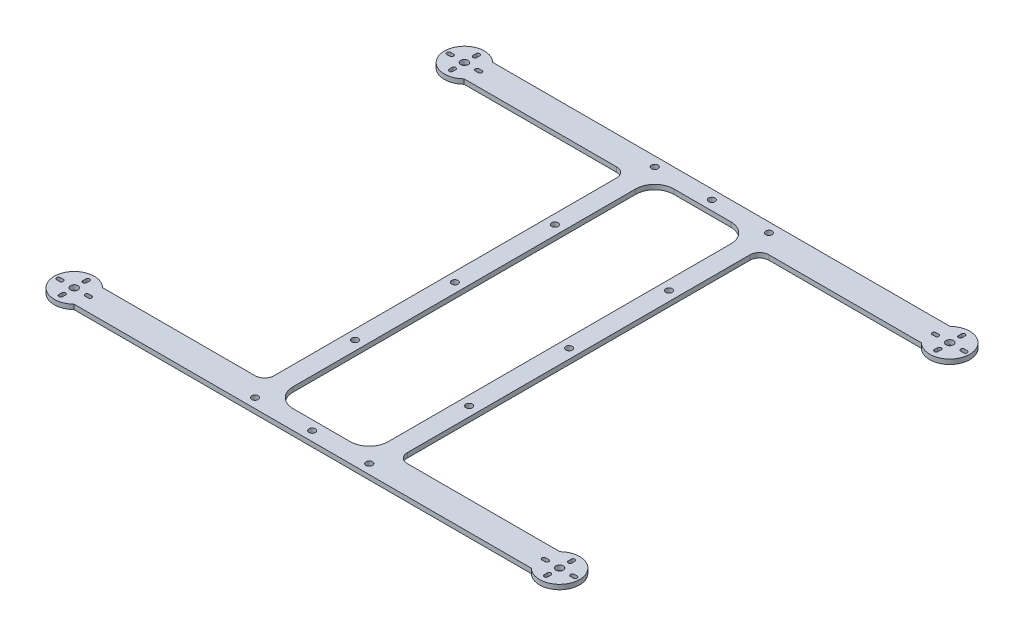
SolidWorks part; units mm, degrees
ref_plane "Front Plane" through (0, 0, 0) normal (0, 0, 1) x (1, 0, 0)
ref_plane "Top Plane" through (0, 0, 0) normal (0, 1, 0) x (1, 0, 0)
ref_plane "Right Plane" through (0, 0, 0) normal (1, 0, 0) x (0, 0, -1)
sketch "Sketch1" plane through (0, 0, 0) normal (0, 1, 0) x (1, 0, 0)
  line L1 (-44.45, 139.7) -> (44.45, 139.7)
  line L2 (-44.45, 120.65) -> (-44.45, -120.65)
  line L3 (-44.45, -139.7) -> (44.45, -139.7)
  line L4 (44.45, 120.65) -> (44.45, -120.65)
  line L5 (44.45, 139.7) -> (161.925, 139.7)
  line L7 (44.45, 120.65) -> (161.925, 120.65)
  line L8 (161.925, 139.7) -> (161.925, 120.65)
  line L14 (0, 0) -> (0, 187.5455) construction
  line L17 (0, 0) -> (-239.6804, 0) construction
  line L21 (0, 0) -> (44.45, 0) construction
  line L22 (-44.45, 120.65) -> (-161.925, 120.65)
  line L23 (-44.45, 139.7) -> (-161.925, 139.7)
  line L24 (-161.925, 139.7) -> (-161.925, 120.65)
  line L37 (-31.75, 127) -> (31.75, 127)
  line L40 (-31.75, 127) -> (-31.75, -127)
  line L43 (-31.75, -127) -> (31.75, -127)
  line L46 (31.75, 127) -> (31.75, -127)
  line L49 (44.45, -120.65) -> (161.925, -120.65)
  line L50 (44.45, -139.7) -> (161.925, -139.7)
  line L51 (161.925, -139.7) -> (161.925, -120.65)
  line L88 (-161.925, -139.7) -> (-161.925, -120.65)
  line L89 (-44.45, -139.7) -> (-161.925, -139.7)
  line L90 (-44.45, -120.65) -> (-161.925, -120.65)
  point P4 (0, 139.7)
  point P6 (-44.45, 0)
  dimension "D4" = 117.475
  dimension "D1" = 279.4
  dimension "D2" = 88.9
  dimension "D3" = 19.05
  dimension "D6" = 12.7
  dimension "D7" = 12.7
  dimension "D8" = 12.7
  dimension "D10" = 117.475
  dimension "D12" = 12.7
  dimension "D18" = 19.05
extrude "Boss-Extrude1" add sketch "Sketch1" along normal blind 3.175
sketch "Sketch4" plane through (0, 3.175, 0) normal (0, 1, 0) x (1, 0, 0)
  line L0 (161.925, 120.65) -> (161.925, 139.7) construction
  line L1 (-161.925, 139.7) -> (-161.925, 120.65) construction
  line L2 (-161.925, -120.65) -> (-161.925, -139.7) construction
  line L3 (161.925, -139.7) -> (161.925, -120.65) construction
  circle A0 centre (161.925, 130.175) radius 13.335
  circle A1 centre (-161.925, 130.175) radius 13.335
  circle A2 centre (-161.925, -130.175) radius 13.335
  circle A3 centre (161.925, -130.175) radius 13.335
  point P18 (161.925, -130.175)
extrude "Boss-Extrude4" add sketch "Sketch4" against normal up to surface (3.175 mm away) up to face at (0, 0, 0)
sketch "Sketch5" plane through (0, 3.175, 0) normal (0, 1, 0) x (1, 0, 0)
  line L0 (151.425, 130.175) -> (153.425, 130.175) construction
  line L1 (151.425, 131.425) -> (153.425, 131.425)
  line L2 (151.425, 128.925) -> (153.425, 128.925)
  line L3 (161.925, 130.175) -> (161.925, 143.51) construction
  line L4 (172.425, 130.175) -> (170.425, 130.175) construction
  line L5 (172.425, 131.425) -> (170.425, 131.425)
  line L6 (172.425, 128.925) -> (170.425, 128.925)
  line L7 (161.925, 139.175) -> (161.925, 137.175) construction
  line L8 (163.175, 139.175) -> (163.175, 137.175)
  line L9 (160.675, 139.175) -> (160.675, 137.175)
  line L10 (161.925, 130.175) -> (175.26, 130.175) construction
  line L11 (161.925, 121.175) -> (161.925, 123.175) construction
  line L12 (163.175, 121.175) -> (163.175, 123.175)
  line L13 (160.675, 121.175) -> (160.675, 123.175)
  line L14 (0, 0) -> (0, 263.0018) construction
  line L15 (0, 0) -> (558.7896, 0) construction
  line L16 (-151.425, 130.175) -> (-153.425, 130.175) construction
  line L17 (-151.425, 131.425) -> (-153.425, 131.425)
  line L18 (-151.425, 128.925) -> (-153.425, 128.925)
  line L19 (-172.425, 130.175) -> (-170.425, 130.175) construction
  line L20 (-172.425, 131.425) -> (-170.425, 131.425)
  line L21 (-172.425, 128.925) -> (-170.425, 128.925)
  line L22 (-161.925, 139.175) -> (-161.925, 137.175) construction
  line L23 (-163.175, 139.175) -> (-163.175, 137.175)
  line L24 (-160.675, 139.175) -> (-160.675, 137.175)
  line L25 (-161.925, 121.175) -> (-161.925, 123.175) construction
  line L26 (-163.175, 121.175) -> (-163.175, 123.175)
  line L27 (-160.675, 121.175) -> (-160.675, 123.175)
  line L28 (-161.925, 130.175) -> (-175.26, 130.175) construction
  line L29 (-161.925, 130.175) -> (-161.925, 143.51) construction
  line L30 (151.425, -130.175) -> (153.425, -130.175) construction
  line L31 (151.425, -131.425) -> (153.425, -131.425)
  line L32 (151.425, -128.925) -> (153.425, -128.925)
  line L33 (161.925, -139.175) -> (161.925, -137.175) construction
  line L34 (163.175, -139.175) -> (163.175, -137.175)
  line L35 (160.675, -139.175) -> (160.675, -137.175)
  line L36 (172.425, -130.175) -> (170.425, -130.175) construction
  line L37 (172.425, -131.425) -> (170.425, -131.425)
  line L38 (172.425, -128.925) -> (170.425, -128.925)
  line L39 (161.925, -121.175) -> (161.925, -123.175) construction
  line L40 (163.175, -121.175) -> (163.175, -123.175)
  line L41 (160.675, -121.175) -> (160.675, -123.175)
  line L42 (161.925, -130.175) -> (175.26, -130.175) construction
  line L43 (161.925, -130.175) -> (161.925, -143.51) construction
  line L44 (-161.925, -130.175) -> (-161.925, -143.51) construction
  line L45 (-161.925, -130.175) -> (-175.26, -130.175) construction
  line L46 (-161.925, -121.175) -> (-161.925, -123.175) construction
  line L47 (-163.175, -121.175) -> (-163.175, -123.175)
  line L48 (-160.675, -121.175) -> (-160.675, -123.175)
  line L49 (-161.925, -139.175) -> (-161.925, -137.175) construction
  line L50 (-163.175, -139.175) -> (-163.175, -137.175)
  line L51 (-160.675, -139.175) -> (-160.675, -137.175)
  line L52 (-172.425, -130.175) -> (-170.425, -130.175) construction
  line L53 (-172.425, -131.425) -> (-170.425, -131.425)
  line L54 (-172.425, -128.925) -> (-170.425, -128.925)
  line L55 (-151.425, -130.175) -> (-153.425, -130.175) construction
  line L56 (-151.425, -131.425) -> (-153.425, -131.425)
  line L57 (-151.425, -128.925) -> (-153.425, -128.925)
  circle A0 centre (161.925, 130.175) radius 2.5
  arc A1 (151.425, 131.425) -> (151.425, 128.925) centre (151.425, 130.175) ccw
  arc A2 (153.425, 128.925) -> (153.425, 131.425) centre (153.425, 130.175) ccw
  arc A3 (152.5924, 120.65) -> (152.5924, 139.7) centre (161.925, 130.175) ccw construction
  arc A4 (172.425, 131.425) -> (172.425, 128.925) centre (172.425, 130.175) cw
  arc A5 (170.425, 128.925) -> (170.425, 131.425) centre (170.425, 130.175) cw
  arc A6 (163.175, 139.175) -> (160.675, 139.175) centre (161.925, 139.175) ccw
  arc A7 (160.675, 137.175) -> (163.175, 137.175) centre (161.925, 137.175) ccw
  arc A8 (163.175, 121.175) -> (160.675, 121.175) centre (161.925, 121.175) cw
  arc A9 (160.675, 123.175) -> (163.175, 123.175) centre (161.925, 123.175) cw
  arc A10 (-151.425, 131.425) -> (-151.425, 128.925) centre (-151.425, 130.175) cw
  arc A11 (-153.425, 128.925) -> (-153.425, 131.425) centre (-153.425, 130.175) cw
  arc A12 (-172.425, 131.425) -> (-172.425, 128.925) centre (-172.425, 130.175) ccw
  arc A13 (-170.425, 128.925) -> (-170.425, 131.425) centre (-170.425, 130.175) ccw
  arc A14 (-163.175, 139.175) -> (-160.675, 139.175) centre (-161.925, 139.175) cw
  arc A15 (-160.675, 137.175) -> (-163.175, 137.175) centre (-161.925, 137.175) cw
  arc A16 (-163.175, 121.175) -> (-160.675, 121.175) centre (-161.925, 121.175) ccw
  arc A17 (-160.675, 123.175) -> (-163.175, 123.175) centre (-161.925, 123.175) ccw
  circle A18 centre (-161.925, 130.175) radius 2.5
  arc A19 (151.425, -131.425) -> (151.425, -128.925) centre (151.425, -130.175) cw
  arc A20 (153.425, -128.925) -> (153.425, -131.425) centre (153.425, -130.175) cw
  arc A21 (163.175, -139.175) -> (160.675, -139.175) centre (161.925, -139.175) cw
  arc A22 (160.675, -137.175) -> (163.175, -137.175) centre (161.925, -137.175) cw
  arc A23 (172.425, -131.425) -> (172.425, -128.925) centre (172.425, -130.175) ccw
  arc A24 (170.425, -128.925) -> (170.425, -131.425) centre (170.425, -130.175) ccw
  arc A25 (163.175, -121.175) -> (160.675, -121.175) centre (161.925, -121.175) ccw
  arc A26 (160.675, -123.175) -> (163.175, -123.175) centre (161.925, -123.175) ccw
  circle A27 centre (161.925, -130.175) radius 2.5
  circle A28 centre (-161.925, -130.175) radius 2.5
  arc A29 (-163.175, -121.175) -> (-160.675, -121.175) centre (-161.925, -121.175) cw
  arc A30 (-160.675, -123.175) -> (-163.175, -123.175) centre (-161.925, -123.175) cw
  arc A31 (-163.175, -139.175) -> (-160.675, -139.175) centre (-161.925, -139.175) ccw
  arc A32 (-160.675, -137.175) -> (-163.175, -137.175) centre (-161.925, -137.175) ccw
  arc A33 (-172.425, -131.425) -> (-172.425, -128.925) centre (-172.425, -130.175) cw
  arc A34 (-170.425, -128.925) -> (-170.425, -131.425) centre (-170.425, -130.175) cw
  arc A35 (-151.425, -131.425) -> (-151.425, -128.925) centre (-151.425, -130.175) ccw
  arc A36 (-153.425, -128.925) -> (-153.425, -131.425) centre (-153.425, -130.175) ccw
  point P5 (152.425, 130.175)
  point P16 (171.425, 130.175)
  point P23 (161.925, 138.175)
  point P31 (161.925, 122.175)
  point P42 (-152.425, 130.175)
  point P49 (-171.425, 130.175)
  point P56 (-161.925, 138.175)
  point P63 (-161.925, 122.175)
  point P74 (152.425, -130.175)
  point P81 (161.925, -138.175)
  point P88 (171.425, -130.175)
  point P95 (161.925, -122.175)
  point P110 (-161.925, -122.175)
  point P117 (-161.925, -138.175)
  point P124 (-171.425, -130.175)
  point P131 (-152.425, -130.175)
  dimension "D1" = 5
  dimension "D2" = 2.5
  dimension "D3" = 2
  dimension "D4" = 19
  dimension "D5" = 2.5
  dimension "D6" = 2
  dimension "D7" = 16
extrude "Motor Holes" cut sketch "Sketch5" against normal through all
sketch "Sketch7" plane through (0, 3.175, 0) normal (0, 1, 0) x (1, 0, 0)
  line L0 (152.5924, 139.7) -> (-152.5924, 139.7) construction
  line L1 (-44.45, 120.65) -> (-44.45, -120.65) construction
  line L2 (0, 0) -> (0, 246.0772) construction
  line L3 (0, 0) -> (301.4392, 0) construction
  circle A0 centre (-38.1, 133.35) radius 2.159
  circle A1 centre (-38.1, 66.675) radius 2.159
  circle A2 centre (-38.1, 0) radius 2.159
  circle A3 centre (-38.1, -66.675) radius 2.159
  circle A5 centre (-38.1, -133.35) radius 2.159
  circle A6 centre (38.1, -133.35) radius 2.159
  circle A7 centre (38.1, -66.675) radius 2.159
  circle A8 centre (38.1, 0) radius 2.159
  circle A9 centre (38.1, 66.675) radius 2.159
  circle A10 centre (38.1, 133.35) radius 2.159
  circle A11 centre (0, 133.35) radius 2.159
  circle A12 centre (0, -133.35) radius 2.159
  dimension "D1" = 4.318
  dimension "D2" = 6.35
  dimension "D3" = 6.35
  dimension "D4" = 66.675
  dimension "D5" = 66.675
  dimension "D6" = 66.675
  dimension "D7" = 66.675
extrude "Cut-Extrude2" cut sketch "Sketch7" against normal through all
fillet "Fillet1" radius 12.7 4 edges at (31.75, 1.5875, 127) (-31.75, 1.5875, 127) (-31.75, 1.5875, -127) (31.75, 1.5875, -127)
fillet "Fillet2" radius 6.35 4 edges at (-44.45, 1.5875, 120.65) (-44.45, 1.5875, -120.65) (44.45, 1.5875, -120.65) (44.45, 1.5875, 120.65)
sketch "Sketch8" plane through (0, 3.175, 0) normal (0, 1, 0) x (1, 0, 0)
  line L0 (152.5924, 139.7) -> (-152.5924, 139.7) construction
  line L1 (0, 139.7) -> (0, 110.7046) construction
  circle A0 centre (-15.7442, 133.35) radius 2.159
  circle A1 centre (15.7442, 133.35) radius 2.159
  dimension "D5" = 4.318
  dimension "D6" = 4.318
  dimension "D1" = 6.35
  dimension "D2" = 6.35
  dimension "D3" = 31.4884
  dimension "D4" = 15.7442
